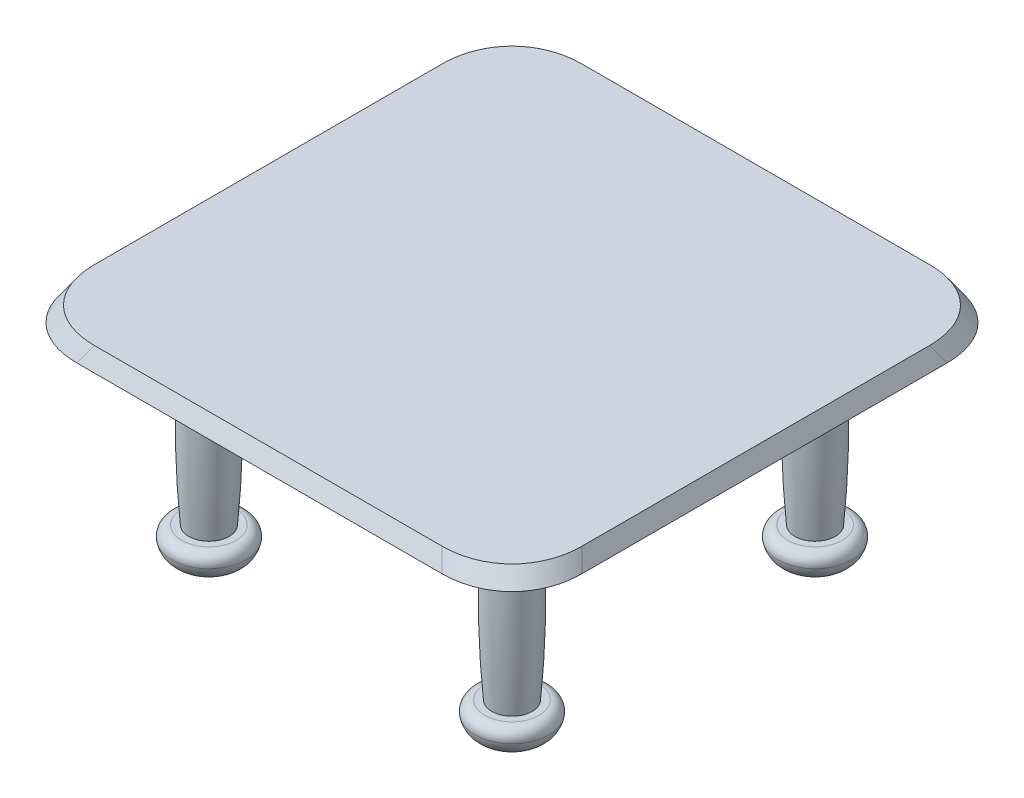
SolidWorks part; units mm, degrees
ref_plane "Front Plane" through (0, 0, 0) normal (0, 0, 1) x (1, 0, 0)
ref_plane "Top Plane" through (0, 0, 0) normal (0, 1, 0) x (1, 0, 0)
ref_plane "Right Plane" through (0, 0, 0) normal (1, 0, 0) x (0, 0, -1)
sketch "Sketch1" plane through (0, 0, 0) normal (0, 0, 1) x (1, 0, 0)
  line L0 (0, 200) -> (0, 0)
  line L1 (0, 0) -> (25, 0)
  line L3 (20, 200) -> (0, 200)
  line L4 (35.2882, 26.6252) -> (20, 26.6252)
  arc A0 (25, 0) -> (35.2882, 26.6252) centre (16.8315, 18.4567) ccw
  arc A1 (20, 26.6252) -> (20, 200) centre (-1034.4279, 113.3126) ccw
  dimension "D1" = 200
  dimension "D2" = 20
  dimension "D3" = 25
revolve "Revolve1" add sketch "Sketch1" angle 360 about L0
fillet "Fillet1" radius 10 1 edges at (-35.2882, 26.6252, 0)
pattern_linear "LPattern2" count 2 spacing 300 along (0, 0, -1) of bodies 101
pattern_linear "LPattern3" count 2 spacing 300 along (-1, 0, 0) of bodies 102 101
sketch "Sketch2" plane through (0, 200, 0) normal (0, 1, 0) x (1, 0, 0)
  line L1 (-400, 400) -> (100, 400)
  line L2 (-400, 400) -> (-400, -100)
  line L3 (-400, -100) -> (100, -100)
  line L4 (100, 400) -> (100, -100)
  circle A0 centre (0, 300) radius 20 construction
  circle A1 centre (-300, 300) radius 20 construction
  circle A2 centre (-300, 0) radius 20 construction
  dimension "D1" = 100
  dimension "D2" = 100
  dimension "D3" = 100
  dimension "D4" = 100
extrude "Boss-Extrude1" add sketch "Sketch2" along normal blind 15 draft 30
fillet "Fillet2" radius 80 4 edges at (-395.6699, 207.5, -395.6699) (-395.6699, 207.5, 95.6699) (95.6699, 207.5, -395.6699) (95.6699, 207.5, 95.6699)
